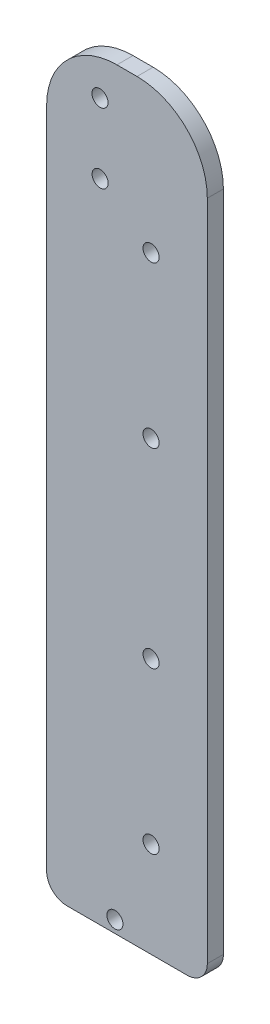
SolidWorks part; units mm, degrees
ref_plane "Front Plane" through (0, 0, 0) normal (0, 0, 1) x (1, 0, 0)
ref_plane "Top Plane" through (0, 0, 0) normal (0, 1, 0) x (1, 0, 0)
ref_plane "Right Plane" through (0, 0, 0) normal (1, 0, 0) x (0, 0, -1)
sketch "Sketch1" plane through (0, 0, 0) normal (0, 0, 1) x (1, 0, 0)
  line L1 (0, -146.6506) -> (0, 146.6506) construction
  line L3 (40.64, 5.08) -> (40.64, 172.72)
  line L5 (35.56, 0) -> (26.416, 0)
  line L7 (66.681, 0) -> (66.681, 88.9) construction
  line L8 (26.416, 0) -> (40.64, 0) construction
  line L9 (26.416, 177.8) -> (26.416, 0) construction
  line L10 (118.1346, 0) -> (-118.1346, 0) construction
  line L11 (66.681, 88.9) -> (0, 88.9) construction
  line L14 (26.416, 0) -> (5.08, 0)
  line L18 (66.681, 88.9) -> (66.681, 177.8) construction
  line L19 (66.681, 177.8) -> (0, 177.8) construction
  line L20 (0, 5.08) -> (0, 172.72)
  line L23 (26.416, 0) -> (20.32, 0) construction
  line L24 (20.32, 0) -> (19.8425, 177.8) construction
  line L25 (20.32, 0) -> (14.732, 0) construction
  line L26 (14.732, 0) -> (14.732, 8.89) construction
  line L27 (14.732, 8.89) -> (14.732, 177.8) construction
  line L28 (26.416, 24.13) -> (0, 24.13) construction
  line L35 (20.32, 0) -> (17.6513, 0) construction
  line L36 (17.6513, 0) -> (17.6513, 177.8) construction
  line L46 (17.78, 190.5) -> (22.86, 190.5)
  line L47 (19.8425, 177.8) -> (19.8425, 190.5) construction
  line L48 (19.8896, 160.274) -> (19.8425, 190.5) construction
  line L49 (19.8425, 190.5) -> (-14.4304, 190.5) construction
  line L50 (19.8896, 160.274) -> (0, 160.274) construction
  circle A0 centre (26.416, 24.13) radius 2.032
  circle A1 centre (26.416, 64.77) radius 2.032
  arc A5 (35.56, 0) -> (40.64, 5.08) centre (35.56, 5.08) ccw
  arc A6 (5.08, 0) -> (0, 5.08) centre (5.08, 5.08) cw
  circle A7 centre (26.416, 113.03) radius 2.032
  circle A8 centre (26.416, 153.67) radius 2.032
  arc A13 (40.64, 172.72) -> (22.86, 190.5) centre (22.86, 172.72) ccw
  arc A14 (0, 172.72) -> (17.78, 190.5) centre (17.78, 172.72) cw
  circle A15 centre (17.272, 3.048) radius 2.032
  circle A16 centre (13.4925, 181.102) radius 2.032
  circle A17 centre (13.531, 163.449) radius 2.032
  point P24 (0, 190.5)
  point P30 (0, 0)
  point P38 (0, 190.5)
  point P42 (0, 185.42)
  point P46 (40.64, 185.0608)
  point P52 (0, 190.5)
  dimension "D7" = 4.064
  dimension "D5" = 24.13
  dimension "D6" = 4.064
  dimension "D9" = 24.13
  dimension "D11" = 88.9
  dimension "D12" = 5.08
  dimension "D13" = 4.064
  dimension "D15" = 4.064
  dimension "D17" = 4.064
  dimension "D19" = 17.78
  dimension "D22" = 4.064
  dimension "D26" = 4.064
  dimension "D20" = 23.368
  dimension "D25" = 6.35
  dimension "D27" = 6.35
  dimension "D29" = 6.35
  dimension "D1" = 190.5
  dimension "D2" = 40.64
  dimension "D3" = 88.9
  dimension "D4" = 14.224
  dimension "D8" = 40.64
  dimension "D10" = 24.13
  dimension "D14" = 3.048
  dimension "D16" = 40.64
  dimension "D18" = 24.13
  dimension "D21" = 30.226
  dimension "D23" = 20.32
  dimension "D24" = 25.908
  dimension "D28" = 64.77
  dimension "D32" = 2.6687
  dimension "0.25" = 9.398
extrude "Boss-Extrude2" add sketch "Sketch1" along normal blind 4.064
